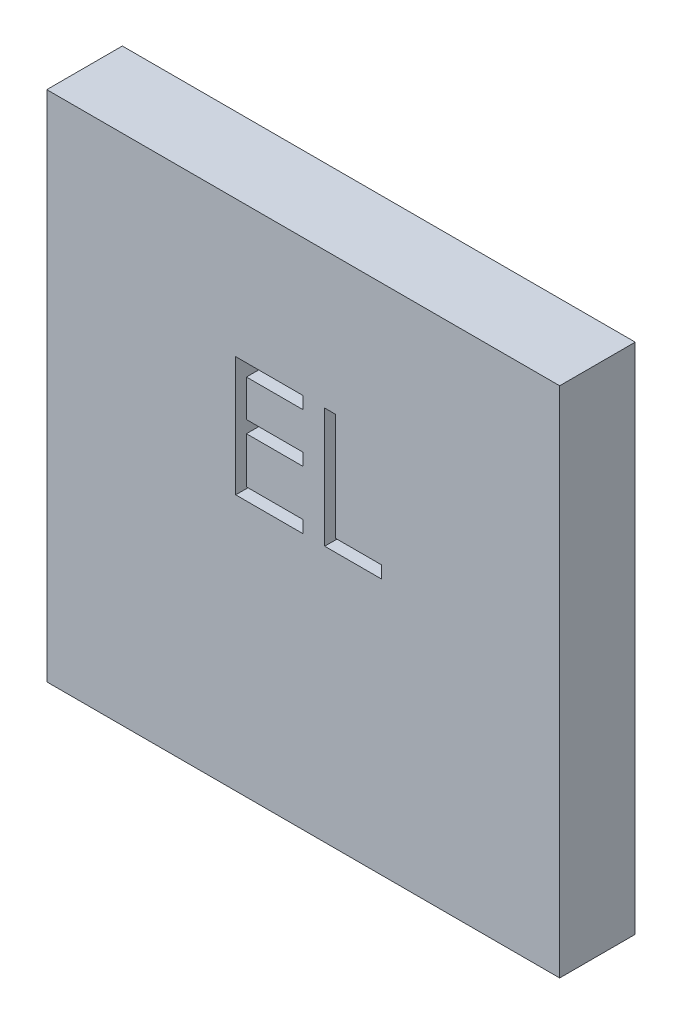
SolidWorks part; units mm, degrees
ref_plane "XY" through (0, 0, 0) normal (0, 0, 1) x (1, 0, 0)
ref_plane "XZ" through (0, 0, 0) normal (0, 1, 0) x (1, 0, 0)
ref_plane "YZ" through (0, 0, 0) normal (1, 0, 0) x (0, 0, -1)
ref_axis "X" through (-88.99, 0, 0) along (1, 0, 0)
ref_axis "Y" through (0, -55, 0) along (0, 1, 0)
ref_axis "Z" through (0, 0, 55) along (0, 0, -1)
sketch "Sketch1" plane through (0, 0, 0) normal (0, 0, 1) x (1, 0, 0)
  line L0 (0, 7.5) -> (15, 7.5) construction
  line L1 (0, 0) -> (15, 0)
  line L2 (0, 0) -> (0, 15)
  line L3 (0, 15) -> (15, 15)
  line L4 (15, 0) -> (15, 15)
  text T0 "EL"
  dimension "D1" = 15
extrude "Boss-Extrude1" add sketch "Sketch1" along normal blind 2.21
